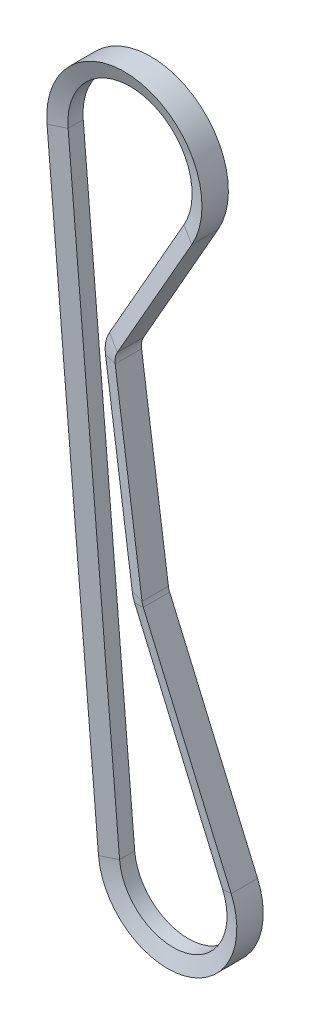
SolidWorks part; units mm, degrees
ref_plane "Front Plane" through (0, 0, 0) normal (0, 0, 1) x (1, 0, 0)
ref_plane "Top Plane" through (0, 0, 0) normal (0, 1, 0) x (1, 0, 0)
ref_plane "Right Plane" through (0, 0, 0) normal (1, 0, 0) x (0, 0, -1)
sketch "Sketch2" plane through (0, 0, 0) normal (0, 0, 1) x (1, 0, 0)
  line L0 (0, 0) -> (1, 0) construction
  line L1 (0, 0) -> (0, 1) construction
  line L12 (-24.9108, -2.11) -> (-43.4772, 217.0846)
  line L14 (8.7448, 205.5753) -> (-18.1154, 158.4828)
  line L15 (-18.8886, 154.4587) -> (-9.2096, 85.1311)
  line L16 (-8.7524, 83.4966) -> (22.9597, 9.892)
  arc A4 (-43.4772, 217.0846) -> (8.7448, 205.5753) centre (-15.5771, 219.4478) cw
  arc A7 (22.9597, 9.892) -> (-24.9108, -2.11) centre (0, 0) cw
  arc A8 (-18.1154, 158.4828) -> (-18.8886, 154.4587) centre (-12.5996, 155.3368) ccw
  arc A9 (-9.2096, 85.1311) -> (-8.7524, 83.4966) centre (-2.9206, 86.0091) ccw
ref_plane "Plane4" through (22.9597, 9.892, 0) normal (0.3957, -0.9184, 0) x (-0.9184, -0.3957, 0)
sketch "Sketch3" plane through (22.9597, 9.892, 0) normal (0.3957, -0.9184, 0) x (-0.9184, -0.3957, 0)
  line L0 (0, -4.7625) -> (0, 4.7625)
  line L1 (0, -4.7625) -> (5.588, -2.7286)
  line L2 (5.588, -2.7286) -> (5.588, 2.7286)
  line L3 (5.588, 2.7286) -> (0, 4.7625)
  line L4 (0, 0) -> (5.588, 0) construction
  dimension "D1" = 9.525
  dimension "D2" = 5.588
  dimension "D3" = 40
sweep "Sweep1" add profiles "Sketch3" path "Sketch2"
